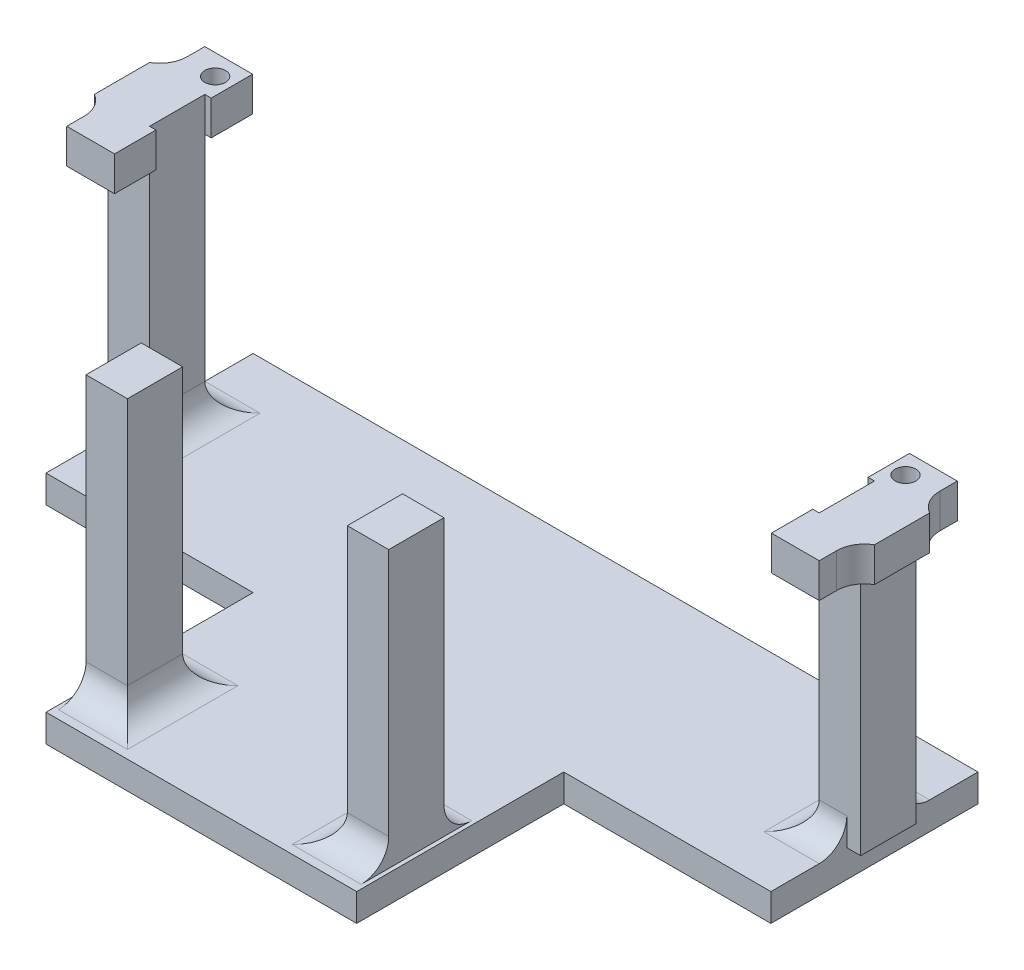
SolidWorks part; units mm, degrees
ref_plane "Front Plane" through (0, 0, 0) normal (0, 0, 1) x (1, 0, 0)
ref_plane "Top Plane" through (0, 0, 0) normal (0, 1, 0) x (1, 0, 0)
ref_plane "Right Plane" through (0, 0, 0) normal (1, 0, 0) x (0, 0, -1)
sketch "Sketch1" plane through (0, 0, 0) normal (0, 1, 0) x (1, 0, 0)
  line L0 (22.5, -15) -> (52.5, -15)
  line L1 (-52.5, 15) -> (52.5, 15)
  line L2 (-52.5, 15) -> (-52.5, -15)
  line L3 (-52.5, -15) -> (52.5, -15)
  line L4 (52.5, 15) -> (52.5, -15)
  line L5 (-52.5, 15) -> (52.5, -15) construction
  line L6 (-52.5, -15) -> (52.5, 15) construction
  line L7 (-22.5, -15) -> (22.5, -15)
  line L8 (-22.5, -15) -> (-22.5, -45)
  line L9 (-22.5, -45) -> (22.5, -45)
  line L10 (22.5, -15) -> (22.5, -45)
  point P0 (0, 0)
  dimension "D1" = 30
  dimension "D2" = 105
  dimension "D3" = 45
  dimension "D4" = 30
  dimension "D5" = 30
extrude "Boss-Extrude1" add sketch "Sketch1" along normal blind 4 contours L10 L3 L8 L9 | L4 L1 L2 L3 region at (0, 0, 30)
sketch "Sketch2" plane through (0, 4, 0) normal (0, 1, 0) x (1, 0, 0)
  line L0 (-51.5, 0) -> (51.5, 0) construction
  line L1 (0, 0) -> (0, -35.7796) construction
  line L2 (-54.5, 4) -> (-48.5, 4)
  line L3 (-54.5, 4) -> (-54.5, -4)
  line L4 (-54.5, -4) -> (-48.5, -4)
  line L5 (-48.5, 4) -> (-48.5, -4)
  line L6 (-54.5, 4) -> (-48.5, -4) construction
  line L7 (-54.5, -4) -> (-48.5, 4) construction
  line L8 (0, -35.7796) -> (-18.9239, -35.7796) construction
  line L10 (-21.9239, -31.7796) -> (-15.9239, -31.7796)
  line L11 (-21.9239, -31.7796) -> (-21.9239, -39.7796)
  line L12 (-21.9239, -39.7796) -> (-15.9239, -39.7796)
  line L13 (-15.9239, -31.7796) -> (-15.9239, -39.7796)
  line L14 (-21.9239, -31.7796) -> (-15.9239, -39.7796) construction
  line L15 (-21.9239, -39.7796) -> (-15.9239, -31.7796) construction
  point P4 (0, 0)
  dimension "D1" = 103
  dimension "D2" = 6
  dimension "D3" = 8
extrude "Boss-Extrude2" add sketch "Sketch2" along normal blind 40
sketch "Sketch3" plane through (0, 44, 0) normal (0, 1, 0) x (1, 0, 0)
  line L0 (-24.2, 0) -> (24.2, 0) construction
  line L1 (-54.5, 4) -> (-47.5711, 4)
  line L2 (-54.5, 4) -> (-54.5, 10)
  line L3 (-54.5, 10) -> (-47.5711, 10)
  line L4 (-47.5711, 4) -> (-47.5711, 10)
  line L5 (-54.5, -10) -> (-47.5711, -10)
  line L6 (-47.5711, -4) -> (-47.5711, -10)
  line L7 (-54.5, -4) -> (-47.5711, -4)
  line L8 (-54.5, -4) -> (-54.5, -10)
  line L10 (-54.5, 4) -> (-56.5, 4)
  line L11 (-54.5, 4) -> (-54.5, -4)
  line L12 (-54.5, -4) -> (-56.5, -4)
  line L13 (-56.5, 4) -> (-56.5, -4)
  circle A0 centre (-50, 7) radius 1.5
  point P16 (0, 0)
  line M6 (-48.5, 4) -> (-54.5, 4)
  line M7 (-54.5, 4) -> (-54.5, -4)
  line M8 (-54.5, -4) -> (-48.5, -4)
  dimension "D2" = 3
  dimension "D1" = 6
  dimension "D3" = 2
extrude "Boss-Extrude3" add sketch "Sketch3" against normal blind 5 contours L10 L13 L12 M7 | L4 L3 L2 A0 M6 | L8 L5 L6 M8 region at (-54.4083, 44, -7) region at (-55.5, 44, 0) region at (-51.0356, 44, 7)
fillet "Fillet2" radius 4 2 edges at (-54.5, 41.5, -4) (-54.5, 41.5, 4)
fillet "Fillet3" radius 4 6 edges at (-18.9239, 4, 39.7796) (-15.9239, 4, 35.7796) (-18.9239, 4, 31.7796) (-50.5, 4, -4) (-50.5, 4, 4) (-48.5, 4, 0)
mirror "Mirror2" about plane through (0, 0, 0) normal (1, 0, 0) of "Fillet3", "Fillet2", "Boss-Extrude3", "Boss-Extrude2"
